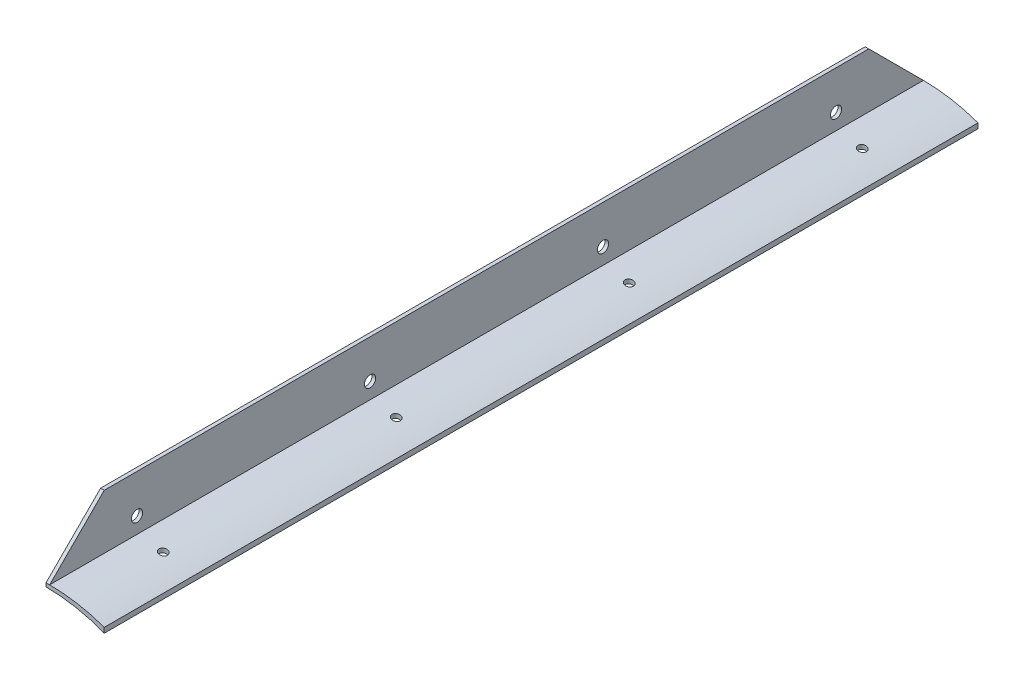
SolidWorks part; units mm, degrees
material "6061-T6 (SS)"
ref_plane "Front Plane" through (0, 0, 0) normal (0, 0, 1) x (1, 0, 0)
ref_plane "Top Plane" through (0, 0, 0) normal (0, 1, 0) x (1, 0, 0)
ref_plane "Right Plane" through (0, 0, 0) normal (1, 0, 0) x (0, 0, -1)
sketch "Sketch1" plane through (0, 0, 0) normal (0, 0, 1) x (1, 0, 0)
  line L0 (0, 0) -> (0, 25.4)
  line L1 (0, 25.4) -> (1.5875, 25.4)
  line L2 (1.5875, 25.4) -> (1.5875, 1.5875)
  line L3 (25.4, -2.5468) -> (25.4, -4.7819)
  arc A0 (0, 0) -> (25.4, -4.7819) centre (0, -69.85) cw
  arc A1 (1.5875, 1.5875) -> (25.4, -2.5468) centre (1.5875, -69.0562) cw
  dimension "D1" = 25.4
  dimension "D5" = 69.85
  dimension "D6" = 70.6437
  dimension "D2" = 23.8125
  dimension "D3" = 1.5875
  dimension "D4" = 25.4
extrude "Extrude1" add sketch "Sketch1" along normal mid plane 381
ref_plane "Plane2" through (0, 0, 0) normal (0, 0, -1) x (-1, 0, 0)
sketch "Sketch2" plane through (0, 0, 0) normal (-1, 0, 0) x (0, 0, 1)
  line L0 (190.5, 25.4) -> (166.6875, 25.4)
  line L1 (190.5, 25.4) -> (-190.5, 25.4) construction
  line L2 (166.6875, 25.4) -> (190.5, 1.5875)
  line L3 (190.5, 25.4) -> (190.5, 0) construction
  line L4 (190.5, 1.5875) -> (190.5, 25.4)
  dimension "D1" = 1.5875
extrude "Extrude2" cut sketch "Sketch2" against normal blind 387.35
mirror "Mirror2" about plane through (0, 0, 0) normal (0, 0, -1) of "Extrude2"
ref_plane "Plane3" through (0, 1.5875, 0) normal (0, 1, 0) x (-1, 0, 0)
sketch "Sketch3" plane through (0, 1.5875, 0) normal (0, 1, 0) x (-1, 0, 0)
  line L0 (-1.5875, -50.8) -> (-13.0175, -50.8) construction
  line L1 (-1.5875, 166.6875) -> (-1.5875, -166.6875) construction
  line L3 (-0.8731, 0) -> (0.8731, 0) construction
  dimension "D1" = 11.43
  dimension "D2" = 50.8
hole_wizard "#6 Clearance Hole1" positions "Sketch6" profile "Sketch7" hole size "#6" standard "Ansi Inch" end condition through all
sketch "Sketch6" plane through (0, 1.5875, 0) normal (0, 1, 0) x (-1, 0, 0)
  point P1 (-13.0175, -50.8)
sketch "Sketch7" plane through (13.0175, 1.5875, -50.8) normal (1, 0, 0) x (0, 0, 1)
  line L0 (0, 0) -> (0, 6.3694)
  line L1 (0, 6.3694) -> (1.8288, 6.3694)
  line L2 (1.8288, 6.3694) -> (1.8288, 0)
  line L5 (1.8288, 0) -> (0, 0)
  line L11 (0, -6.35) -> (0, 107.95) construction
  dimension "Thru Hole Dia." = 3.6576
  dimension "Thru Hole Depth" = 6.3694
sketch "Sketch8" plane through (1.5875, 0, 0) normal (1, 0, 0) x (0, 0, -1)
  line L0 (50.8, 1.5875) -> (50.8, 8.5725) construction
  dimension "D1" = 6.985
hole_wizard "#10 (0.1935) Diameter Hole1" positions "3DSketch2" profile "Sketch10" hole size "#10" standard "Ansi Inch" end condition through all
sketch3d "3DSketch2"
  point P0 (1.5875, 8.5725, -50.8)
sketch "Sketch10" plane through (1.5875, 8.5725, -50.8) normal (0, 1, 0) x (0, 0, -1)
  line L0 (0, 0) -> (0, 1.5875)
  line L1 (0, 1.5875) -> (2.4574, 1.5875)
  line L2 (2.4574, 1.5875) -> (2.4574, 0)
  line L5 (2.4574, 0) -> (0, 0)
  line L11 (0, -6.35) -> (0, 107.95) construction
  dimension "Thru Hole Dia." = 4.9149
  dimension "Thru Hole Depth" = 1.5875
pattern_linear "LPattern1" count 3 spacing 101.6 along (0, 0, 1) count 2 spacing 101.6 along (0, 0, -1) of "#10 (0.1935) Diameter Hole1", "#6 Clearance Hole1"
